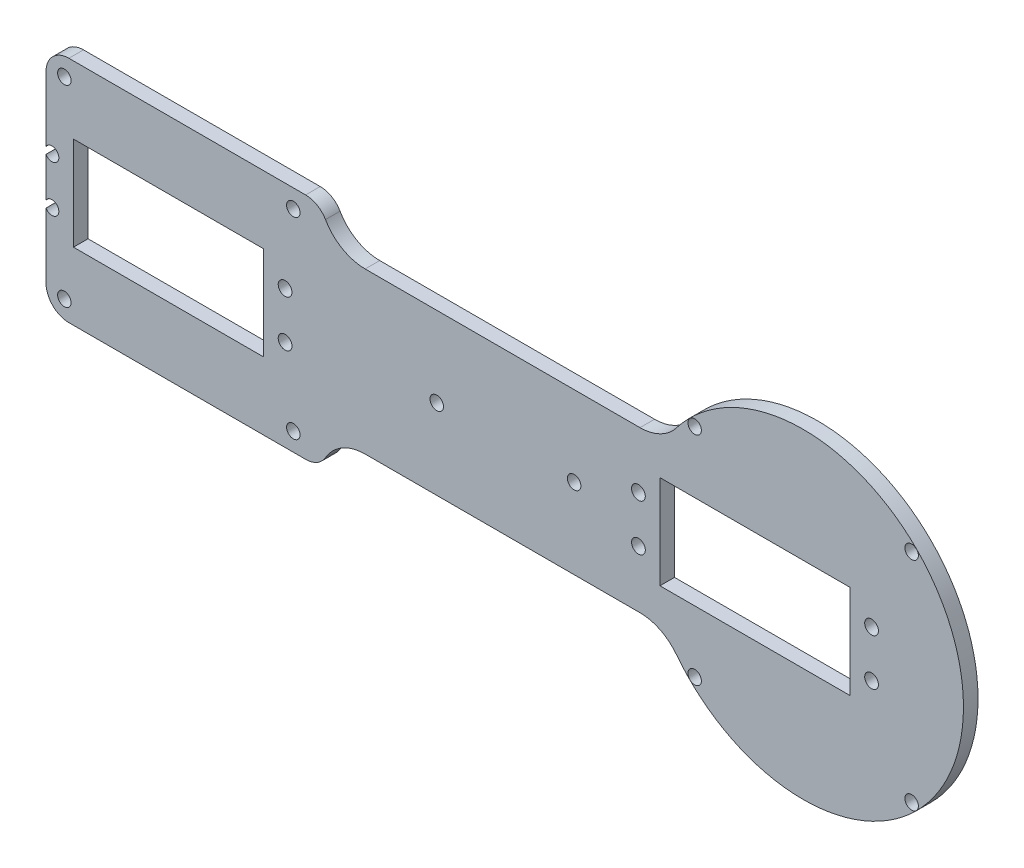
SolidWorks part; units mm, degrees
ref_plane "Front Plane" through (0, 0, 0) normal (0, 0, 1) x (1, 0, 0)
ref_plane "Top Plane" through (0, 0, 0) normal (0, 1, 0) x (1, 0, 0)
ref_plane "Right Plane" through (0, 0, 0) normal (1, 0, 0) x (0, 0, -1)
sketch "Sketch1" plane through (0, 0, 0) normal (0, 0, 1) x (1, 0, 0)
  line L1 (-105.3109, 17.5) -> (-30.3109, 17.5)
  line L2 (-105.3109, 17.5) -> (-105.3109, -17.5)
  line L3 (-105.3109, -17.5) -> (-30.3109, -17.5)
  line L5 (-105.3109, 17.5) -> (-30.3109, -17.5) construction
  line L6 (-105.3109, -17.5) -> (-30.3109, 17.5) construction
  arc A0 (-30.3109, -17.5) -> (-30.3109, 17.5) centre (0, 0) ccw
  point P4 (-67.8109, 0)
  dimension "D1" = 70
  dimension "D2" = 75
  dimension "D3" = 35
extrude "Boss-Extrude1" add sketch "Sketch1" along normal blind 3.18
fillet "Fillet1" radius 10 2 edges at (-30.3109, 17.5, 1.59) (-30.3109, -17.5, 1.59)
sketch "Sketch2" plane through (-105.3109, 0, 0) normal (-1, 0, 0) x (0, 0, 1)
  line L0 (3.18, 17.5) -> (3.18, -17.5) construction
  line L1 (3.18, -25) -> (0, -25)
  line L2 (3.18, -25) -> (3.18, 25)
  line L3 (3.18, 25) -> (0, 25)
  line L4 (0, -25) -> (0, 25)
  line L5 (3.18, -25) -> (0, 25) construction
  line L6 (3.18, 25) -> (0, -25) construction
  line L9 (0, 0) -> (5.297, 0) construction
  point P0 (1.59, 0)
  dimension "D1" = 3.18
  dimension "D2" = 50
extrude "Boss-Extrude2" add sketch "Sketch2" along normal blind 60
fillet "Fillet3" radius 10 2 edges at (-105.3109, -17.5, 1.59) (-105.3109, 17.5, 1.59)
fillet "Fillet4" radius 5 4 edges at (-105.3109, 25, 1.59) (-165.3109, 25, 1.59) (-165.3109, -25, 1.59) (-105.3109, -25, 1.59)
sketch "Sketch3" plane through (0, 0, 0) normal (0, 0, -1) x (-1, 0, 0)
  line L0 (165.3109, 20) -> (165.3109, -20) construction
  line L1 (-10.2391, 10.225) -> (31.2609, 10.225)
  line L2 (-10.2391, 10.225) -> (-10.2391, -10.225)
  line L3 (-10.2391, -10.225) -> (31.2609, -10.225)
  line L4 (31.2609, 10.225) -> (31.2609, -10.225)
  line L5 (-10.2391, 10.225) -> (31.2609, -10.225) construction
  line L6 (-10.2391, -10.225) -> (31.2609, 10.225) construction
  point P0 (10.5109, 0)
  dimension "D1" = 41.5
  dimension "D2" = 20.45
  dimension "D3" = 134.05
extrude "Cut-Extrude1" cut sketch "Sketch3" against normal through all
sketch "Sketch4" plane through (0, 0, 0) normal (0, 0, -1) x (-1, 0, 0)
  line L0 (165.3109, 20) -> (165.3109, -20) construction
  line L1 (159.3109, 10.225) -> (117.8109, 10.225)
  line L2 (159.3109, 10.225) -> (159.3109, -10.225)
  line L3 (159.3109, -10.225) -> (117.8109, -10.225)
  line L4 (117.8109, 10.225) -> (117.8109, -10.225)
  line L5 (159.3109, 10.225) -> (117.8109, -10.225) construction
  line L6 (159.3109, -10.225) -> (117.8109, 10.225) construction
  point P0 (138.5609, 0)
  dimension "D1" = 41.5
  dimension "D2" = 20.45
  dimension "D3" = 6
extrude "Cut-Extrude2" cut sketch "Sketch4" against normal blind 3.18
sketch "Sketch5" plane through (0, 0, 0) normal (0, 0, -1) x (-1, 0, 0)
  line L0 (0, 0) -> (0, 35) construction
  line L1 (0, 0) -> (23.6881, 23.6881) construction
  circle A0 centre (23.6881, 23.6881) radius 1.47
  arc A5 (27.7041, 21.3889) -> (27.7041, -21.3889) centre (0, 0) ccw construction
  dimension "D1" = 2.94
  dimension "D2" = 45
  dimension "D7" = 33.5
extrude "Cut-Extrude3" cut sketch "Sketch5" against normal blind 3.18
pattern_circular "CirPattern1" count 4 over 360 about axis through (0, 0, 3.18) along (0, 0, -1) of "Cut-Extrude3" reverse direction yes
sketch "Sketch6" plane through (0, 0, 0) normal (0, 0, -1) x (-1, 0, 0)
  line L0 (160.3109, -25) -> (108.6188, -25) construction
  line L1 (165.3109, 20) -> (165.3109, -20) construction
  circle A0 centre (161.3109, -21) radius 1.47
  circle A1 centre (111.3109, -21) radius 1.47
  dimension "D1" = 2.94
  dimension "D3" = 4
  dimension "D4" = 50
  dimension "D2" = 4
extrude "Cut-Extrude4" cut sketch "Sketch6" against normal blind 3.18
mirror "Mirror1" about plane through (0, 0, 0) normal (0, 1, 0) of "Cut-Extrude4"
sketch "Sketch7" plane through (0, 0, 0) normal (0, 0, -1) x (-1, 0, 0)
  line L0 (117.8109, 10.225) -> (117.8109, -10.225) construction
  line L1 (117.8109, 0) -> (84.9162, 0) construction
  line L2 (159.3109, -10.225) -> (159.3109, 10.225) construction
  line L3 (164.0109, -5.08) -> (164.0109, 5.08) construction
  circle A0 centre (113.1109, -5.08) radius 1.5
  circle A1 centre (113.1109, 5.08) radius 1.5
  circle A2 centre (164.0109, -5.08) radius 1.5
  circle A3 centre (164.0109, 5.08) radius 1.5
  dimension "D1" = 3
  dimension "D4" = 3
  dimension "D5" = 4.7
  dimension "D2" = 4.7
  dimension "D3" = 5.08
extrude "Cut-Extrude5" cut sketch "Sketch7" against normal blind 3.18
sketch "Sketch8" plane through (0, 0, 0) normal (0, 0, -1) x (-1, 0, 0)
  line L0 (95.6284, -17.5) -> (35.6195, -17.5) construction
  circle A0 centre (80, 0) radius 1.47
  circle A1 centre (50, 0) radius 1.47
  dimension "D1" = 2.94
  dimension "D2" = 30
  dimension "D4" = 17.5
  dimension "D3" = 50
extrude "Cut-Extrude6" cut sketch "Sketch8" against normal blind 3.18
sketch "Sketch9" plane through (0, 0, 0) normal (0, 0, -1) x (-1, 0, 0)
  line L0 (31.2609, -10.225) -> (31.2609, 10.225) construction
  line L1 (31.2609, 0) -> (44.7816, 0) construction
  line L2 (-10.2391, 10.225) -> (-10.2391, -10.225) construction
  circle A0 centre (35.9609, -5.08) radius 1.5
  circle A1 centre (35.9609, 5.08) radius 1.5
  circle A2 centre (-14.9391, -5.08) radius 1.5
  circle A3 centre (-14.9391, 5.08) radius 1.5
  dimension "D1" = 3
  dimension "D2" = 4.7
  dimension "D3" = 10.16
  dimension "D5" = 4.7
  dimension "D4" = 10.16
extrude "Cut-Extrude7" cut sketch "Sketch9" against normal blind 3.18
sketch "Sketch10" [suppressed] plane through (0, 0, 0) normal (0, 0, -1) x (-1, 0, 0)
  line L0 (159.3109, -10.225) -> (159.3109, 10.225) construction
  line L1 (165.8109, -3.5) -> (159.3109, -3.5)
  line L2 (165.8109, -3.5) -> (165.8109, 3.5)
  line L3 (165.8109, 3.5) -> (159.3109, 3.5)
  line L4 (159.3109, -3.5) -> (159.3109, 3.5)
  line L5 (165.8109, -3.5) -> (159.3109, 3.5) construction
  line L6 (165.8109, 3.5) -> (159.3109, -3.5) construction
  line L9 (165.3109, 0) -> (159.3109, 0) construction
  line L10 (165.3109, 20) -> (165.3109, -20) construction
  point P0 (162.5609, 0)
  dimension "D1" = 6.5
  dimension "D2" = 7
extrude "Cut-Extrude8" [suppressed] cut sketch "Sketch10" against normal blind 3.18
sketch "Sketch11" [suppressed] plane through (0, 0, 0) normal (0, 0, -1) x (-1, 0, 0)
  line L0 (-10.2391, 10.225) -> (-10.2391, -10.225) construction
  line L1 (-16.7391, -3.5) -> (-10.2391, -3.5)
  line L2 (-16.7391, -3.5) -> (-16.7391, 3.5)
  line L3 (-16.7391, 3.5) -> (-10.2391, 3.5)
  line L4 (-10.2391, -3.5) -> (-10.2391, 3.5)
  line L5 (-16.7391, -3.5) -> (-10.2391, 3.5) construction
  line L6 (-16.7391, 3.5) -> (-10.2391, -3.5) construction
  point P0 (-13.4891, 0)
  dimension "D1" = 6.5
  dimension "D2" = 7
extrude "Cut-Extrude9" [suppressed] cut sketch "Sketch11" against normal blind 3.18
